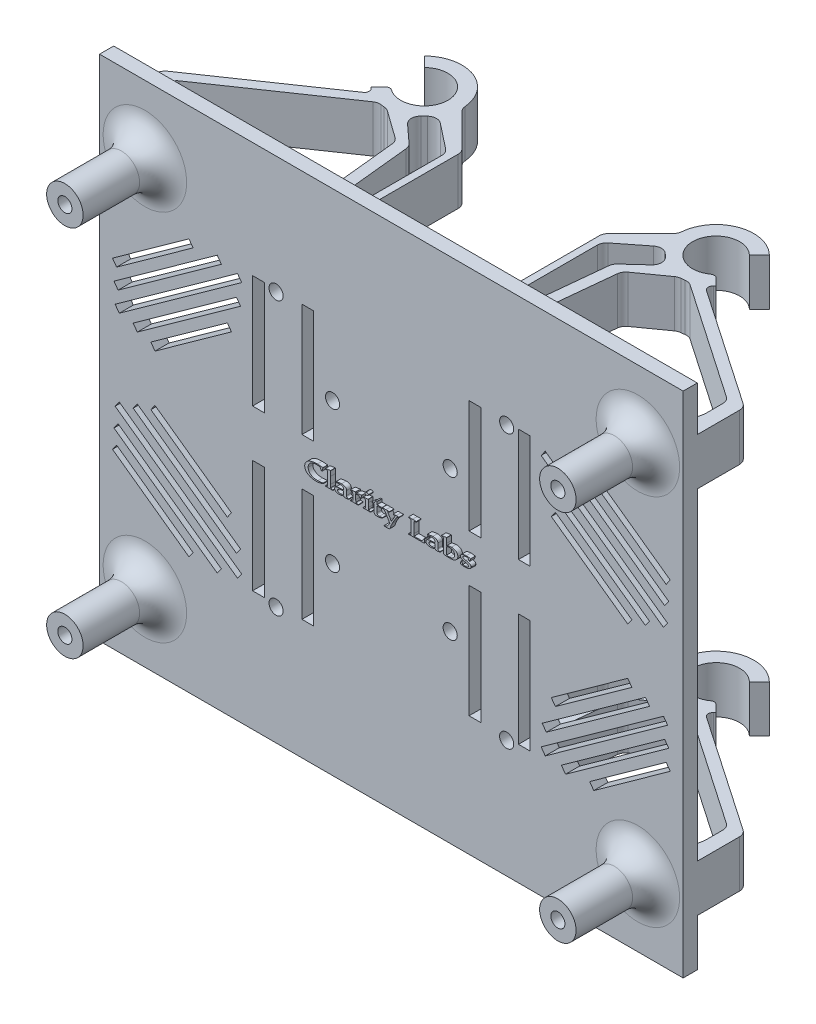
SolidWorks part; units mm, degrees
ref_plane "Front Plane" through (0, 0, 0) normal (0, 0, 1) x (1, 0, 0)
ref_plane "Top Plane" through (0, 0, 0) normal (0, 1, 0) x (1, 0, 0)
ref_plane "Right Plane" through (0, 0, 0) normal (1, 0, 0) x (0, 0, -1)
sketch "Sketch1" plane through (0, 0, 0) normal (0, 1, 0) x (1, 0, 0)
  line L0 (0, 8) -> (0, -8) construction
  line L1 (-8, 0) -> (8, 0) construction
  line L2 (-5.6569, 5.6569) -> (-3.5355, 3.5355)
  line L4 (31, 0) -> (31, 33.0539) construction
  line L6 (-3.5355, -3.5355) -> (-5.6569, -5.6569)
  line L18 (11.6803, -35) -> (14.4901, -35)
  line L19 (-31, -38) -> (93, -38)
  line L20 (-28, -35) -> (0.1335, -35)
  line L25 (0.1335, -35) -> (9.25, -35)
  line L28 (62, 8) -> (62, -8) construction
  line L41 (65.5355, -3.5355) -> (67.6569, -5.6569)
  line L44 (67.6569, 5.6569) -> (65.5355, 3.5355)
  line L45 (0, -8) -> (7, -13)
  line L46 (7, -13) -> (9.25, -35)
  line L47 (8, 0) -> (16, -8)
  line L48 (16, -8) -> (16, -35)
  line L52 (3.5, -7.1937) -> (9.3878, -12.584)
  line L53 (9.3878, -12.584) -> (11.6803, -35)
  line L55 (14.4901, -35) -> (14.4901, -9.7945)
  line L56 (6.9901, -3.8909) -> (14.4901, -9.7945)
  line L57 (-31, -38) -> (-31, -25)
  line L58 (-31, -25) -> (-4.3208, -6.7328)
  line L59 (-2.0004, -7.7459) -> (-28, -25.5477)
  line L60 (-28, -25.5477) -> (-28, -35)
  line L61 (46, -8) -> (46, -35)
  line L62 (47.5099, -35) -> (47.5099, -9.7945)
  line L63 (54, 0) -> (46, -8)
  line L64 (55.0099, -3.8909) -> (47.5099, -9.7945)
  line L65 (62, -8) -> (55, -13)
  line L66 (58.5, -7.1937) -> (52.6122, -12.584)
  line L67 (52.6122, -12.584) -> (50.3197, -35)
  line L68 (55, -13) -> (52.75, -35)
  line L69 (93, -38) -> (93, -25)
  line L70 (90, -25.5477) -> (90, -35)
  line L71 (64.0004, -7.7459) -> (90, -25.5477)
  line L72 (93, -25) -> (66.3208, -6.7328)
  line L73 (3.5, -7.1937) -> (6.9901, -3.8909)
  line L74 (55.0099, -3.8909) -> (58.5, -7.1937)
  line L75 (47.5099, -35) -> (50.3197, -35)
  line L76 (52.75, -35) -> (61.8665, -35)
  line L78 (16, -35) -> (46, -35)
  line L79 (61.8665, -35) -> (90, -35)
  arc A0 (-3.5355, -3.5355) -> (-3.5355, 3.5355) centre (0, 0) ccw
  arc A1 (-5.6569, -5.6569) -> (-4.3208, -6.7328) centre (0, 0) ccw
  arc A2 (-2.0004, -7.7459) -> (0, -8) centre (0, 0) ccw
  arc A3 (8, 0) -> (-5.6569, 5.6569) centre (0, 0) ccw
  arc A4 (54, 0) -> (67.6569, 5.6569) centre (62, 0) cw
  arc A5 (64.0004, -7.7459) -> (62, -8) centre (62, 0) cw
  arc A6 (67.6569, -5.6569) -> (66.3208, -6.7328) centre (62, 0) cw
  arc A7 (65.5355, -3.5355) -> (65.5355, 3.5355) centre (62, 0) cw
  point P49 (31, -35)
  point P56 (31, -38)
  dimension "D1" = 16
  dimension "D2" = 10
  dimension "D3" = 3
  dimension "D4" = 5.6569
  dimension "D5" = 2.4177
  dimension "D6" = 45
  dimension "D7" = 3.5
  dimension "D8" = 31
  dimension "D9" = 6.9901
  dimension "D10" = 7.9826
  dimension "D11" = 25.2055
  dimension "D12" = 9.5448
  dimension "D13" = 4.3208
  dimension "D14" = 28
  dimension "D15" = 15
  dimension "D16" = 13
  dimension "D17" = 16
  dimension "D18" = 12.4523
  dimension "D19" = 35
  dimension "D20" = 27
  dimension "D21" = 3
  dimension "D22" = 31
  dimension "D23" = 6.75
  dimension "D24" = 0.1335
  dimension "D25" = 33.0539
  dimension "D26" = 9
  dimension "D27" = 22
  dimension "D28" = 35
  dimension "D29" = 35
extrude "Boss-Extrude1" add sketch "Sketch1" along normal blind 10
ref_plane "Plane1" through (0, 88.5, 0) normal (0, 1, 0) x (1, 0, 0)
sketch "Sketch7" plane through (0, 88.5, 0) normal (0, 1, 0) x (1, 0, 0)
  line L0 (0, 8) -> (0, -8) construction
  line L1 (-8, 0) -> (8, 0) construction
  line L2 (-5.6569, 5.6569) -> (-3.5355, 3.5355)
  line L3 (31, 0) -> (31, 33.0539) construction
  line L4 (-3.5355, -3.5355) -> (-5.6569, -5.6569)
  line L5 (11.6803, -35) -> (14.4901, -35)
  line L6 (-31, -38) -> (93, -38)
  line L7 (-28, -35) -> (0.1335, -35)
  line L8 (0.1335, -35) -> (9.25, -35)
  line L9 (62, 8) -> (62, -8) construction
  line L10 (65.5355, -3.5355) -> (67.6569, -5.6569)
  line L11 (67.6569, 5.6569) -> (65.5355, 3.5355)
  line L12 (0, -8) -> (7, -13)
  line L13 (7, -13) -> (9.25, -35)
  line L14 (8, 0) -> (16, -8)
  line L15 (16, -8) -> (16, -35)
  line L16 (3.5, -7.1937) -> (9.3878, -12.584)
  line L17 (9.3878, -12.584) -> (11.6803, -35)
  line L18 (14.4901, -35) -> (14.4901, -9.7945)
  line L19 (6.9901, -3.8909) -> (14.4901, -9.7945)
  line L20 (-31, -38) -> (-31, -25)
  line L21 (-31, -25) -> (-4.3208, -6.7328)
  line L22 (-2.0004, -7.7459) -> (-28, -25.5477)
  line L23 (-28, -25.5477) -> (-28, -35)
  line L24 (46, -8) -> (46, -35)
  line L25 (47.5099, -35) -> (47.5099, -9.7945)
  line L26 (54, 0) -> (46, -8)
  line L27 (55.0099, -3.8909) -> (47.5099, -9.7945)
  line L28 (62, -8) -> (55, -13)
  line L29 (58.5, -7.1937) -> (52.6122, -12.584)
  line L30 (52.6122, -12.584) -> (50.3197, -35)
  line L31 (55, -13) -> (52.75, -35)
  line L32 (93, -38) -> (93, -25)
  line L33 (90, -25.5477) -> (90, -35)
  line L34 (64.0004, -7.7459) -> (90, -25.5477)
  line L35 (93, -25) -> (66.3208, -6.7328)
  line L36 (3.5, -7.1937) -> (6.9901, -3.8909)
  line L37 (55.0099, -3.8909) -> (58.5, -7.1937)
  line L38 (47.5099, -35) -> (50.3197, -35)
  line L39 (52.75, -35) -> (61.8665, -35)
  line L40 (16, -35) -> (46, -35)
  line L41 (61.8665, -35) -> (90, -35)
  line L42 (93, -38) -> (93, -25) construction
  line L43 (-31, -38) -> (93, -38) construction
  arc A0 (-3.5355, -3.5355) -> (-3.5355, 3.5355) centre (0, 0) ccw
  arc A1 (-5.6569, -5.6569) -> (-4.3208, -6.7328) centre (0, 0) ccw
  arc A2 (-2.0004, -7.7459) -> (0, -8) centre (0, 0) ccw
  arc A3 (8, 0) -> (-5.6569, 5.6569) centre (0, 0) ccw
  arc A4 (54, 0) -> (67.6569, 5.6569) centre (62, 0) cw
  arc A5 (64.0004, -7.7459) -> (62, -8) centre (62, 0) cw
  arc A6 (67.6569, -5.6569) -> (66.3208, -6.7328) centre (62, 0) cw
  arc A7 (65.5355, -3.5355) -> (65.5355, 3.5355) centre (62, 0) cw
  point P43 (31, -35)
  point P48 (31, -38)
  dimension "D1" = 16
  dimension "D2" = 10
  dimension "D3" = 45
  dimension "D4" = 31
  dimension "D5" = 3
  dimension "D6" = 5.6569
  dimension "D7" = 3.5
  dimension "D8" = 4.3208
  dimension "D9" = 6.9901
  dimension "D10" = 35
  dimension "D11" = 3
  dimension "D12" = 31
  dimension "D13" = 15
  dimension "D14" = 27
  dimension "D15" = 6.75
  dimension "D16" = 9
  dimension "D17" = 22
  dimension "D18" = 2.4177
  dimension "D19" = 7.9826
  dimension "D20" = 25.2055
  dimension "D21" = 9.5448
  dimension "D22" = 28
  dimension "D23" = 13
  dimension "D24" = 12.4523
  dimension "D25" = 0.1335
  dimension "D26" = 16
  dimension "D27" = 33.0539
  dimension "D28" = 35
  dimension "D29" = 35
extrude "Boss-Extrude5" add sketch "Sketch7" against normal blind 10 separate body
sketch "Sketch8" plane through (0, 0, 0) normal (0, -1, 0) x (1, 0, 0)
  line L0 (-31, 25) -> (-31, 38) construction
  line L1 (-31, 35) -> (93, 35)
  line L2 (-31, 35) -> (-31, 38)
  line L3 (-31, 38) -> (93, 38)
  line L4 (93, 35) -> (93, 38)
extrude "Boss-Extrude6" add sketch "Sketch8" along normal blind 10 and the other way blind 98
sketch "Sketch10" plane through (0, 0, 38) normal (0, 0, 1) x (1, 0, 0)
  line L0 (31, 98) -> (31, -10) construction
  line L1 (93, 98) -> (-31, 98) construction
  line L2 (93, -10) -> (-31, -10) construction
  line L3 (31, 44) -> (-31, 44) construction
  line L4 (-31, 98) -> (-31, -10) construction
  line L5 (-31, 44) -> (93, 44) construction
  line L6 (93, 98) -> (93, -10) construction
  circle A0 centre (-21.375, 83.625) radius 3.875
  circle A1 centre (-21.375, 83.625) radius 1.5
  circle A2 centre (83.375, 83.625) radius 1.5
  circle A3 centre (83.375, 83.625) radius 3.875
  circle A4 centre (83.375, 4.375) radius 3.875
  circle A5 centre (83.375, 4.375) radius 1.5
  circle A6 centre (-21.375, 4.375) radius 1.5
  circle A7 centre (-21.375, 4.375) radius 3.875
  dimension "D1" = 7.75
  dimension "D2" = 3
  dimension "D3" = 52.375
  dimension "D4" = 39.625
extrude "Boss-Extrude7" add sketch "Sketch10" along normal blind 17
sketch "Sketch11" plane through (0, 0, 35) normal (0, 0, -1) x (-1, 0, 0)
  line L0 (-50, 49.5) -> (-47.5, 49.5)
  line L5 (-31, 98) -> (-31, -10) construction
  line L6 (31, 98) -> (-93, 98) construction
  line L7 (31, -10) -> (-93, -10) construction
  line L12 (-54, 78.5) -> (-46, 78.5) construction
  line L13 (-47.5, 73.5) -> (-50, 73.5)
  line L14 (-47.5, 73.5) -> (-47.5, 49.5)
  line L15 (-47.5, 15.5) -> (-50, 15.5)
  line L16 (-50, 73.5) -> (-50, 49.5)
  line L17 (-50, 39.5) -> (-47.5, 39.5)
  line L18 (-50, 39.5) -> (-50, 15.5)
  line L19 (-47.5, 39.5) -> (-47.5, 15.5)
  line L20 (-14.5, 39.5) -> (-14.5, 15.5)
  line L21 (-12, 39.5) -> (-14.5, 39.5)
  line L22 (-12, 39.5) -> (-12, 15.5)
  line L23 (-14.5, 15.5) -> (-12, 15.5)
  line L24 (-14.5, 73.5) -> (-14.5, 49.5)
  line L25 (-12, 49.5) -> (-14.5, 49.5)
  line L26 (-12, 73.5) -> (-12, 49.5)
  line L27 (-14.5, 73.5) -> (-12, 73.5)
  line L28 (-93, 44.25) -> (31, 44.25) construction
  line L29 (-93, 78.5) -> (-93, 10) construction
  line L30 (31, 78.5) -> (31, 10) construction
  line L31 (-4, 39.5) -> (-1.5, 39.5)
  line L32 (-54, 98) -> (-54, -10) construction
  line L33 (-60.5, 39.5) -> (-60.5, 15.5)
  line L34 (-58, 39.5) -> (-60.5, 39.5)
  line L35 (-58, 39.5) -> (-58, 15.5)
  line L36 (-60.5, 15.5) -> (-58, 15.5)
  line L37 (-60.5, 73.5) -> (-60.5, 49.5)
  line L38 (-58, 49.5) -> (-60.5, 49.5)
  line L39 (-58, 73.5) -> (-58, 49.5)
  line L40 (-60.5, 73.5) -> (-58, 73.5)
  line L41 (-4, 39.5) -> (-4, 15.5)
  line L42 (-1.5, 15.5) -> (-4, 15.5)
  line L43 (-1.5, 39.5) -> (-1.5, 15.5)
  line L44 (-1.5, 73.5) -> (-4, 73.5)
  line L45 (-4, 73.5) -> (-4, 49.5)
  line L46 (-4, 49.5) -> (-1.5, 49.5)
  line L47 (-1.5, 73.5) -> (-1.5, 49.5)
  line L49 (12.006, 73.5) -> (28.2591, 61.8451)
  line L50 (12.006, 73.5) -> (11.1319, 72.281)
  line L51 (28.2591, 61.8451) -> (27.385, 60.6261)
  line L52 (11.1319, 72.281) -> (27.385, 60.6261)
  line L53 (6, 73.5) -> (27.9417, 57.7659)
  line L54 (6, 73.5) -> (5.1259, 72.281)
  line L55 (27.9417, 57.7659) -> (27.0676, 56.5469)
  line L56 (5.1259, 72.281) -> (27.0676, 56.5469)
  line L58 (1.6939, 72.281) -> (27.6988, 53.6332)
  line L59 (1.6939, 72.281) -> (0.8197, 71.062)
  line L60 (27.6988, 53.6332) -> (26.8247, 52.4142)
  line L61 (0.8197, 71.062) -> (26.8247, 52.4142)
  line L63 (1.2568, 71.6715) -> (27.2617, 53.0237) construction
  line L65 (19.2266, 49.2489) -> (20.1007, 50.4679)
  line L66 (3.8476, 62.1228) -> (20.1007, 50.4679)
  line L67 (2.9735, 60.9039) -> (3.8476, 62.1228)
  line L68 (2.9735, 60.9039) -> (19.2266, 49.2489)
  line L69 (22.9883, 50.8583) -> (23.8625, 52.0773)
  line L70 (1.9208, 67.8114) -> (23.8625, 52.0773)
  line L71 (1.0467, 66.5924) -> (1.9208, 67.8114)
  line L72 (1.0467, 66.5924) -> (22.9883, 50.8583)
  line L73 (28.2591, 26.6549) -> (27.385, 27.8739)
  line L74 (11.1319, 16.219) -> (27.385, 27.8739)
  line L75 (12.006, 15) -> (11.1319, 16.219)
  line L76 (12.006, 15) -> (28.2591, 26.6549)
  line L77 (27.9417, 30.7341) -> (27.0676, 31.9531)
  line L78 (5.1259, 16.219) -> (27.0676, 31.9531)
  line L79 (6, 15) -> (5.1259, 16.219)
  line L80 (6, 15) -> (27.9417, 30.7341)
  line L81 (27.6988, 34.8668) -> (26.8247, 36.0858)
  line L82 (0.8197, 17.438) -> (26.8247, 36.0858)
  line L83 (1.6939, 16.219) -> (0.8197, 17.438)
  line L84 (1.6939, 16.219) -> (27.6988, 34.8668)
  line L85 (1.0467, 21.9076) -> (22.9883, 37.6417)
  line L86 (1.0467, 21.9076) -> (1.9208, 20.6886)
  line L87 (1.9208, 20.6886) -> (23.8625, 36.4227)
  line L88 (22.9883, 37.6417) -> (23.8625, 36.4227)
  line L89 (2.9735, 27.5961) -> (19.2266, 39.2511)
  line L90 (2.9735, 27.5961) -> (3.8476, 26.3772)
  line L91 (3.8476, 26.3772) -> (20.1007, 38.0321)
  line L92 (19.2266, 39.2511) -> (20.1007, 38.0321)
  line L93 (-74.006, 15) -> (-90.2591, 26.6549)
  line L94 (-74.006, 15) -> (-73.1319, 16.219)
  line L95 (-73.1319, 16.219) -> (-89.385, 27.8739)
  line L96 (-90.2591, 26.6549) -> (-89.385, 27.8739)
  line L97 (-68, 15) -> (-89.9417, 30.7341)
  line L98 (-68, 15) -> (-67.1259, 16.219)
  line L99 (-67.1259, 16.219) -> (-89.0676, 31.9531)
  line L100 (-89.9417, 30.7341) -> (-89.0676, 31.9531)
  line L101 (-63.6939, 16.219) -> (-89.6988, 34.8668)
  line L102 (-63.6939, 16.219) -> (-62.8197, 17.438)
  line L103 (-62.8197, 17.438) -> (-88.8247, 36.0858)
  line L104 (-89.6988, 34.8668) -> (-88.8247, 36.0858)
  line L105 (-63.0467, 21.9076) -> (-63.9208, 20.6886)
  line L106 (-63.9208, 20.6886) -> (-85.8625, 36.4227)
  line L107 (-84.9883, 37.6417) -> (-85.8625, 36.4227)
  line L108 (-63.0467, 21.9076) -> (-84.9883, 37.6417)
  line L109 (-64.9735, 27.5961) -> (-65.8476, 26.3772)
  line L110 (-65.8476, 26.3772) -> (-82.1007, 38.0321)
  line L111 (-81.2266, 39.2511) -> (-82.1007, 38.0321)
  line L112 (-64.9735, 27.5961) -> (-81.2266, 39.2511)
  line L113 (-90.2591, 61.8451) -> (-89.385, 60.6261)
  line L114 (-73.1319, 72.281) -> (-89.385, 60.6261)
  line L115 (-74.006, 73.5) -> (-73.1319, 72.281)
  line L116 (-74.006, 73.5) -> (-90.2591, 61.8451)
  line L117 (-89.9417, 57.7659) -> (-89.0676, 56.5469)
  line L118 (-67.1259, 72.281) -> (-89.0676, 56.5469)
  line L119 (-68, 73.5) -> (-67.1259, 72.281)
  line L120 (-68, 73.5) -> (-89.9417, 57.7659)
  line L121 (-89.6988, 53.6332) -> (-88.8247, 52.4142)
  line L122 (-62.8197, 71.062) -> (-88.8247, 52.4142)
  line L123 (-63.6939, 72.281) -> (-62.8197, 71.062)
  line L124 (-63.6939, 72.281) -> (-89.6988, 53.6332)
  line L125 (-63.0467, 66.5924) -> (-84.9883, 50.8583)
  line L126 (-63.0467, 66.5924) -> (-63.9208, 67.8114)
  line L127 (-63.9208, 67.8114) -> (-85.8625, 52.0773)
  line L128 (-84.9883, 50.8583) -> (-85.8625, 52.0773)
  line L129 (-64.9735, 60.9039) -> (-81.2266, 49.2489)
  line L130 (-64.9735, 60.9039) -> (-65.8476, 62.1228)
  line L131 (-65.8476, 62.1228) -> (-82.1007, 50.4679)
  line L132 (-81.2266, 49.2489) -> (-82.1007, 50.4679)
  point P16 (-48.75, 49.5)
  point P49 (1.2568, 71.6715)
  dimension "D1" = 58
  dimension "D2" = 5
  dimension "D3" = 2.5
  dimension "D4" = 16.5
  dimension "D5" = 24
  dimension "D6" = 10
  dimension "D7" = 4
  dimension "D8" = 20
  dimension "D9" = 1.5
  dimension "D10" = 1.5
  dimension "D11" = 1.5
  dimension "D12" = 2
  dimension "D13" = 2
  dimension "D14" = 7.5
  dimension "D15" = 27
  dimension "D16" = 6.6259
  dimension "D17" = 32
  dimension "D18" = 0
  dimension "D19" = 0
extrude "Cut-Extrude3" cut sketch "Sketch11" against normal through all
sketch "Sketch13" plane through (0, 0, 38) normal (0, 0, 1) x (1, 0, 0)
  line L0 (31, 98) -> (31, -10) construction
  line L1 (93, 98) -> (-31, 98) construction
  line L2 (93, -10) -> (-31, -10) construction
  line L3 (-31, 44) -> (93, 44) construction
  line L4 (-31, 98) -> (-31, -10) construction
  line L5 (93, 98) -> (93, -10) construction
  circle A1 centre (6.5, 73) radius 1.5
  circle A2 centre (55.5, 73) radius 1.5
  circle A3 centre (55.5, 15) radius 1.5
  circle A4 centre (6.5, 15) radius 1.5
  circle A5 centre (18.5, 59) radius 1.5
  circle A6 centre (43.5, 59) radius 1.5
  circle A7 centre (43.5, 29) radius 1.5
  circle A8 centre (18.5, 29) radius 1.5
  dimension "D1" = 29
  dimension "D2" = 3
  dimension "D4" = 3
  dimension "D3" = 24.5
  dimension "D5" = 12.5
  dimension "D6" = 15
extrude "Cut-Extrude4" cut sketch "Sketch13" against normal through all
sketch "Sketch14" plane through (0, 0, 38) normal (0, 0, 1) x (1, 0, 0)
  text T0 "Clarity Labs" font "Constantia" height 3.175
  dimension "D1" = 43.5
  dimension "D2" = 13.25
extrude "Boss-Extrude8" add sketch "Sketch14" along normal blind 1
fillet "Fillet5" radius 5 4 edges at (79.5, 83.625, 38) (79.5, 4.375, 38) (-25.25, 4.375, 38) (-25.25, 83.625, 38)
fillet "Fillet8" radius 2 11 edges at (62, 83.5, 8) (55, 83.5, 13) (55.0099, 83.5, 3.8909) (58.5, 83.5, 7.1937) (64.0004, 83.5, 7.7459) (90, 83.5, 25.5477) (93, 83.5, 25) (46, 83.5, 8) (54, 83.5, 0) (47.5099, 83.5, 9.7945) (52.6122, 83.5, 12.584)
fillet "Fillet10" radius 1 1 edges at (66.3208, 83.5, 6.7328)
fillet "Fillet11" radius 1 1 edges at (65.5355, 83.5, 3.5355)
fillet "Fillet27" 2 edges at (50.3197, 83.5, 35) (47.5099, 83.5, 35) type full round first side face at (51.4272, 83.5, 24.1708) second side face at (47.5099, 83.5, 22.8827) middle face at (57, 73, 35)
fillet "Fillet28" radius 5 2 edges at (52.75, 83.5, 35) (90, 83.5, 35)
fillet "Fillet29" radius 5 6 edges at (90, 5, 35) (52.75, 5, 35) (-28, 5, 35) (9.25, 5, 35) (9.25, 83.5, 35) (-28, 83.5, 35)
fillet "Fillet30" radius 1 3 edges at (66.3208, 5, 6.7328) (-4.3208, 83.5, 6.7328) (-4.3208, 5, 6.7328)
fillet "Fillet31" radius 2 19 edges at (8, 5, 0) (16, 5, 8) (9.3878, 5, 12.584) (3.5, 5, 7.1937) (54, 5, 0) (46, 5, 8) (58.5, 5, 7.1937) (52.6122, 5, 12.584) (47.5099, 5, 9.7945) (55.0099, 5, 3.8909) (62, 5, 8) (64.0004, 5, 7.7459) (-2.0004, 5, 7.7459) (0, 5, 8) (6.9901, 5, 3.8909) (14.4901, 5, 9.7945) (7, 5, 13) (-31, 83.5, 25) (-31, 5, 25)
fillet "Fillet32" radius 1 3 edges at (-3.5355, 83.5, 3.5355) (-3.5355, 5, 3.5355) (65.5355, 5, 3.5355)
fillet "Fillet33" 2 edges at (50.3197, 5, 35) (47.5099, 5, 35) type full round first side face at (51.4272, 5, 24.1708) second side face at (47.5099, 5, 22.8827) middle face at (57, 73, 35)
fillet "Fillet36" 2 edges at (11.6803, 83.5, 35) (14.4901, 83.5, 35) type full round first side face at (10.534, 83.5, 23.792) second side face at (14.4901, 83.5, 22.3972) middle face at (57, 73, 35)
fillet "Fillet37" 2 edges at (14.4901, 5, 35) (11.6803, 5, 35) type full round first side face at (14.4901, 5, 22.8827) second side face at (10.5728, 5, 24.1708) middle face at (57, 73, 35)
fillet "Fillet38" radius 2 13 edges at (-2.0004, 83.5, 7.7459) (0, 83.5, 8) (6.9901, 83.5, 3.8909) (3.5, 83.5, 7.1937) (-28, 83.5, 25.5477) (16, 83.5, 8) (9.3878, 83.5, 12.584) (14.4901, 83.5, 9.7945) (7, 83.5, 13) (-28, 5, 25.5477) (55, 5, 13) (93, 5, 25) (90, 5, 25.5477)
fillet "Fillet39" radius 2 1 edges at (8, 83.5, 0)
fillet "Fillet40" radius 2 4 edges at (16, 5, 35) (16, 83.5, 35) (46, 5, 35) (46, 83.5, 35)
